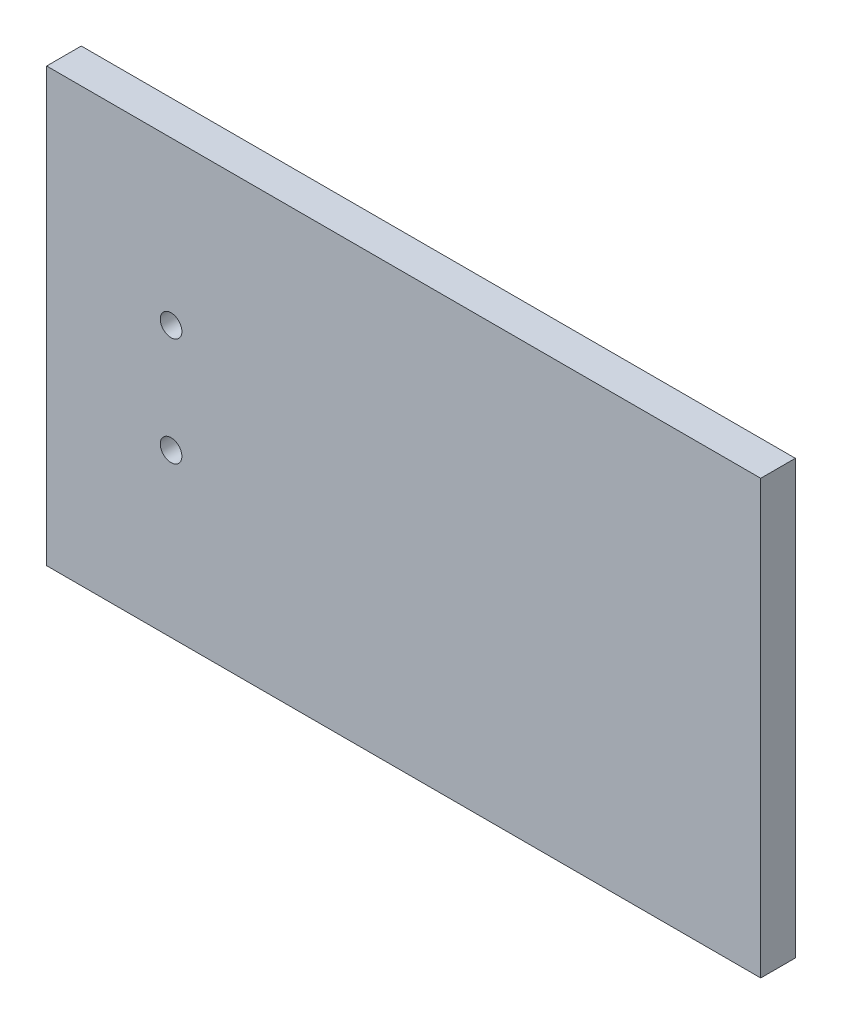
SolidWorks part; units mm, degrees
ref_plane "Front Plane" through (0, 0, 0) normal (0, 0, 1) x (1, 0, 0)
ref_plane "Top Plane" through (0, 0, 0) normal (0, 1, 0) x (1, 0, 0)
ref_plane "Right Plane" through (0, 0, 0) normal (1, 0, 0) x (0, 0, -1)
sketch "Sketch1" plane through (0, 0, 0) normal (0, 1, 0) x (1, 0, 0)
  line L0 (-6, 0) -> (6, 0) construction
  line L1 (6, -20) -> (-6, -20)
  line L2 (6, -20) -> (6, 20)
  line L3 (6, 20) -> (-6, 20)
  line L4 (-6, -20) -> (-6, 20)
  line L5 (6, -20) -> (-6, 20) construction
  line L6 (6, 20) -> (-6, -20) construction
  line L7 (0, -5) -> (0, 5) construction
  circle A0 centre (0, 5) radius 1.25
  circle A1 centre (0, -5) radius 1.25
  point P0 (0, 0)
  dimension "D3" = 5
  dimension "D4" = 2.5
  dimension "D1" = 40
  dimension "D2" = 12
extrude "Hinge " [suppressed] add sketch "Sketch1" along normal blind 5
sketch "Sketch2" [suppressed] plane through (6, 0, 0) normal (1, 0, 0) x (0, 0, -1)
  line L0 (0, 0) -> (0, 5) construction
  line L1 (-20, 0) -> (20, 0) construction
  line L2 (-20, 5) -> (20, 5) construction
  line L3 (-20, 2.5) -> (20, 2.5) construction
  line L4 (-20, 5) -> (-20, 0) construction
  line L5 (20, 5) -> (20, 0) construction
  line L7 (-5, 0) -> (-15, 0)
  line L8 (-5, 0) -> (-5, 5)
  line L9 (-5, 5) -> (-15, 5)
  line L10 (-15, 0) -> (-15, 5)
  line L11 (-5, 0) -> (-15, 5) construction
  line L12 (-5, 5) -> (-15, 0) construction
  line L13 (15, 0) -> (5, 0)
  line L14 (15, 0) -> (15, 5)
  line L15 (15, 5) -> (5, 5)
  line L16 (5, 0) -> (5, 5)
  line L17 (15, 0) -> (5, 5) construction
  line L18 (15, 5) -> (5, 0) construction
  point P12 (-10, 2.5)
  point P17 (10, 2.5)
  dimension "D1" = 5
  dimension "D2" = 5
  dimension "D3" = 10
extrude "Hinge Extrude 1" [suppressed] add sketch "Sketch2" along normal blind 5
sketch "Sketch14" [suppressed] plane through (6, 0, 0) normal (1, 0, 0) x (0, 0, -1)
  line L1 (-5, 0) -> (5, 0)
  line L2 (-5, 0) -> (-5, 5)
  line L3 (-5, 5) -> (5, 5)
  line L4 (5, 0) -> (5, 5)
  line L5 (-20, 0) -> (-15, 0)
  line L6 (-20, 0) -> (-20, 5)
  line L7 (-20, 5) -> (-15, 5)
  line L8 (-15, 0) -> (-15, 5)
  line L9 (15, 0) -> (20, 0)
  line L10 (15, 0) -> (15, 5)
  line L11 (15, 5) -> (20, 5)
  line L12 (20, 0) -> (20, 5)
extrude "Cut Away" [suppressed] cut sketch "Sketch14" against normal blind 1
sketch "Sketch3" [suppressed] plane through (0, 0, -15) normal (0, 0, -1) x (-1, 0, 0)
  line L0 (-11, 0) -> (-5, 0) construction
  line L3 (-5, 5) -> (-5, 0) construction
  circle A0 centre (-9, 2.5) radius 1.5
  dimension "D1" = 3
  dimension "D2" = 2.5
  dimension "D3" = 4
extrude "Hole Cut 1" [suppressed] cut sketch "Sketch3" against normal through all both and the other way through all
fillet "Fillet Holes 1" [suppressed] radius 0.5
chamfer "Chamfer 1" [suppressed] distance 1.5 angle 45
sketch "Sketch4" [suppressed] plane through (6, 0, 0) normal (1, 0, 0) x (0, 0, -1)
  line L0 (0, 0) -> (0, 5) construction
  line L1 (-20, 0) -> (20, 0) construction
  line L2 (-20, 5) -> (20, 5) construction
  line L4 (4.5, 0) -> (-4.5, 0)
  line L5 (4.5, 0) -> (4.5, 5)
  line L6 (4.5, 5) -> (-4.5, 5)
  line L7 (-4.5, 0) -> (-4.5, 5)
  line L8 (4.5, 0) -> (-4.5, 5) construction
  line L9 (4.5, 5) -> (-4.5, 0) construction
  point P6 (0, 2.5)
  dimension "D1" = 5
  dimension "D2" = 9
extrude "Hinge Extrude 2" [suppressed] add sketch "Sketch4" along normal blind 5
sketch "Sketch15" [suppressed] plane through (6, 0, 0) normal (1, 0, 0) x (0, 0, -1)
  line L1 (-20, 0) -> (-4.5, 0)
  line L2 (-20, 0) -> (-20, 5)
  line L3 (-20, 5) -> (-4.5, 5)
  line L4 (-4.5, 0) -> (-4.5, 5)
  line L5 (4.5, 0) -> (20, 0)
  line L6 (4.5, 0) -> (4.5, 5)
  line L7 (4.5, 5) -> (20, 5)
  line L8 (20, 0) -> (20, 5)
extrude "Cut Away 2" [suppressed] cut sketch "Sketch15" against normal blind 1
sketch "Sketch6" [suppressed] plane through (0, 0, -4.5) normal (0, 0, -1) x (-1, 0, 0)
  line L0 (-5, 5) -> (-5, 0) construction
  line L3 (-11, 0) -> (-5, 0) construction
  circle A0 centre (-9, 2.5) radius 1.5
  dimension "D1" = 3
  dimension "D2" = 4
  dimension "D3" = 2.5
extrude "Hole Cut 2 " [suppressed] cut sketch "Sketch6" against normal through all
chamfer "Chamfer2" [suppressed] distance 1.5 angle 45
fillet "Fillet Holes 2" [suppressed] radius 0.5
sketch "Sketch7" [suppressed] plane through (0, 0, 0) normal (0, 0, 1) x (1, 0, 0)
  circle A0 centre (0, 0) radius 1
  dimension "D1" = 2
extrude "Hinge Bar" [suppressed] add sketch "Sketch7" along normal blind 39
sketch "Sketch8" [suppressed] plane through (0, 0, 0) normal (0, 0, -1) x (-1, 0, 0)
  circle A0 centre (0, 0) radius 1.5
  dimension "D1" = 3
extrude "Hinge Bar Holder" [suppressed] add sketch "Sketch8" along normal blind 1
chamfer "Hinge Bar Holder Fillet" [suppressed] distance 0.5 angle 45
sketch "Sketch11" plane through (0, 0, 0) normal (0, 0, 1) x (1, 0, 0)
  line L1 (-33, 20) -> (33, 20)
  line L2 (-33, 20) -> (-33, -20)
  line L3 (-33, -20) -> (33, -20)
  line L4 (33, 20) -> (33, -20)
  line L5 (-33, 20) -> (33, -20) construction
  line L6 (-33, -20) -> (33, 20) construction
  point P0 (0, 0)
  dimension "D1" = 40
  dimension "D2" = 66
extrude "Hole Side Thing" add sketch "Sketch11" along normal blind 3.2
sketch "Sketch12" plane through (0, 0, 3.2) normal (0, 0, 1) x (1, 0, 0)
  line L0 (0, 0) -> (-33, 0) construction
  line L1 (-33, 20) -> (-33, -20) construction
  line L2 (-33, 20) -> (-33, -20) construction
  circle A0 centre (-21.5, 5) radius 1
  circle A1 centre (-21.5, -5) radius 1
  dimension "D1" = 2
  dimension "D3" = 11.5
  dimension "D2" = 5
extrude "Holes for Hole Side Thing" cut sketch "Sketch12" against normal blind 3.2
sketch "Sketch13" [suppressed] plane through (0, 0, 39) normal (0, 0, 1) x (1, 0, 0)
  circle A0 centre (0, 0) radius 1.5
  dimension "D1" = 3
extrude "Boss-Extrude1" [suppressed] add sketch "Sketch13" along normal blind 1
chamfer "Chamfer4" [suppressed] distance 0.5 angle 45
